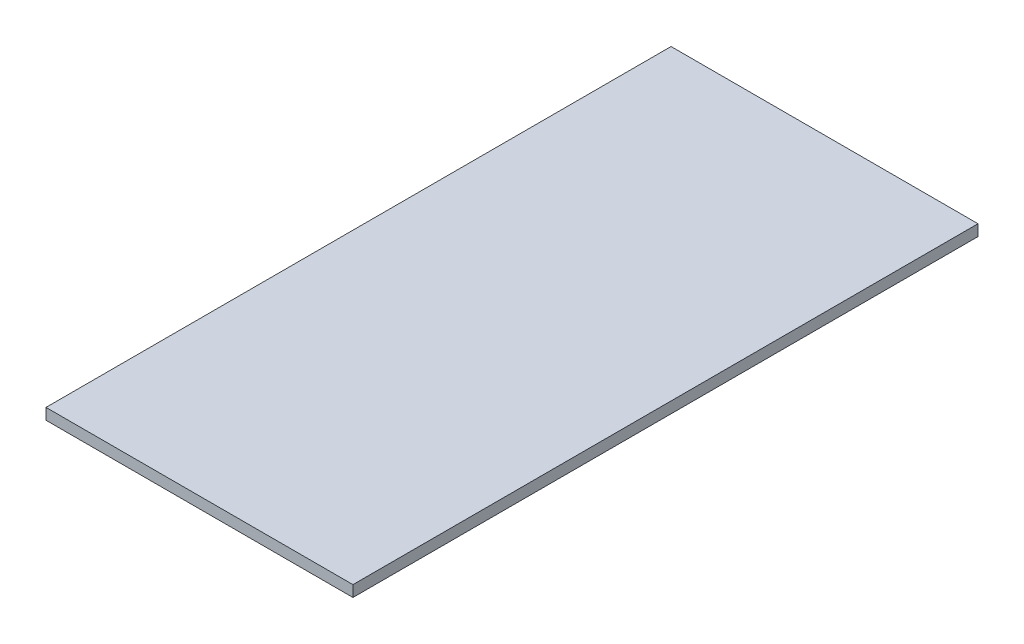
SolidWorks part; units mm, degrees
material "PC High Viscosity"
ref_plane "Front Plane" through (0, 0, 0) normal (0, 0, 1) x (1, 0, 0)
ref_plane "Top Plane" through (0, 0, 0) normal (0, 1, 0) x (1, 0, 0)
ref_plane "Right Plane" through (0, 0, 0) normal (1, 0, 0) x (0, 0, -1)
sketch "Sketch1" plane through (0, 0, 0) normal (0, 1, 0) x (1, 0, 0)
  line L1 (-87.3125, -177.8) -> (87.3125, -177.8)
  line L2 (-87.3125, -177.8) -> (-87.3125, 177.8)
  line L3 (-87.3125, 177.8) -> (87.3125, 177.8)
  line L4 (87.3125, -177.8) -> (87.3125, 177.8)
  line L5 (-87.3125, -177.8) -> (87.3125, 177.8) construction
  line L6 (-87.3125, 177.8) -> (87.3125, -177.8) construction
  point P0 (0, 0)
  dimension "D1" = 174.625
  dimension "D2" = 355.6
extrude "Boss-Extrude1" add sketch "Sketch1" along normal blind 6.35
